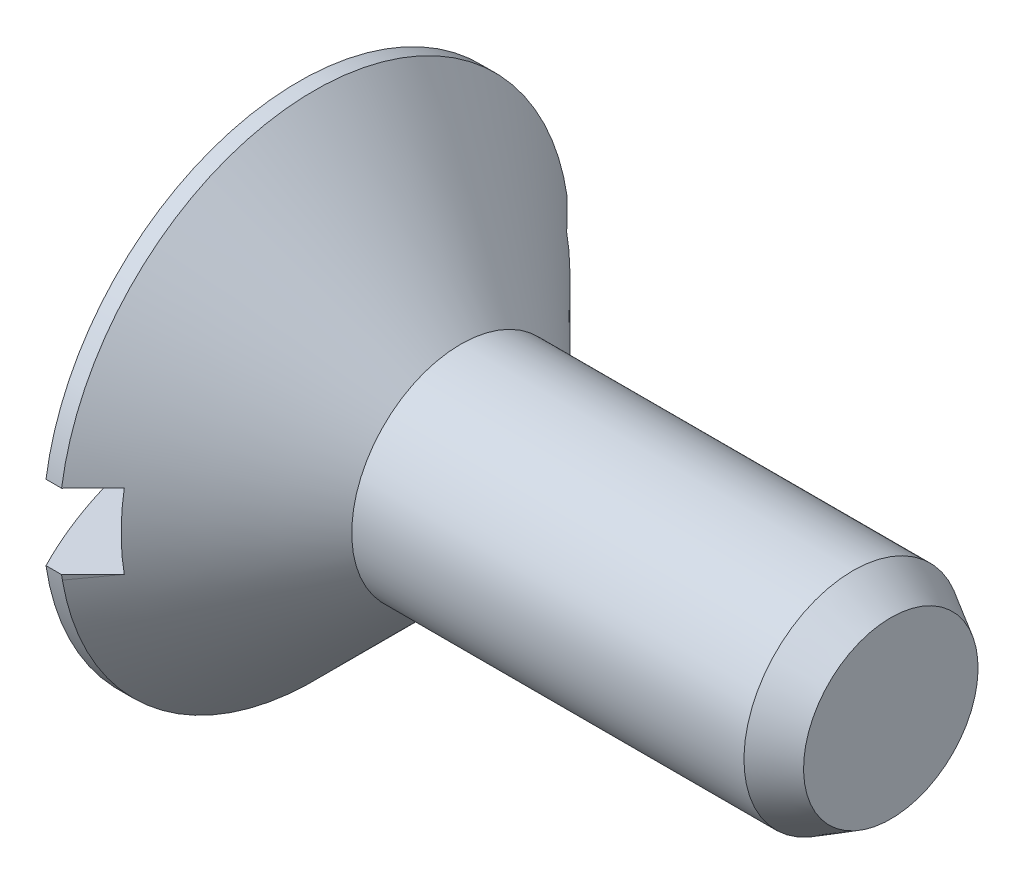
SolidWorks part; units mm, degrees
ref_plane "Front" through (0, 0, 0) normal (0, 0, 1) x (1, 0, 0)
ref_plane "Top" through (0, 0, 0) normal (0, 1, 0) x (1, 0, 0)
ref_plane "Right" through (0, 0, 0) normal (1, 0, 0) x (0, 0, -1)
sketch "Sketch1" plane through (0, 0, 0) normal (0, 0, 1) x (1, 0, 0)
  line L0 (0, 4.1) -> (0.25, 4.1)
  line L1 (0.25, 4.1) -> (2.6, 1.75)
  line L2 (2.6, 1.75) -> (9.5, 1.75)
  line L3 (9.5, 1.75) -> (9.5, 0)
  line L4 (9.5, 0) -> (0, 0)
  line L5 (0, 0) -> (0, 4.1) construction
  line L6 (6.6207, 0) -> (-1, 0) construction
  line L7 (-1, 0) -> (-1, -0.1422) construction
  line L8 (0, 0) -> (-1, 0)
  arc A1 (0, 4.1) -> (-1, 0) centre (7.905, 0) ccw
  dimension "D1" = 45
  dimension "k" = 2.6
revolve "Revolve1" add sketch "Sketch1" angle 360 about L6
cosmetic thread "ThreadCosmetic" [suppressed] parameters "D2"=3.2
sketch "Sketch2" plane through (0, 0, 0) normal (0, 0, 1) x (1, 0, 0)
  line L1 (-1, 0.6) -> (0.75, 0.6)
  line L2 (-1, 0.6) -> (-1, -0.6)
  line L3 (-1, -0.6) -> (0.75, -0.6)
  line L4 (0.75, 0.6) -> (0.75, -0.6)
  line L5 (0, 0) -> (-1, 0) construction
  arc A0 (0, 4.1) -> (-1, 0) centre (7.905, 0) ccw construction
  dimension "n" = 1.2
  dimension "t" = 1.75
extrude "Cut-Extrude1" cut sketch "Sketch2" against normal through all and the other way through all
chamfer "Chamfer1" distance 0.35 angle 60 1 edges at (9.5, 1.75, 0) first distance on face at (9.5, 1.75, 0)
sketch "Sketch4" plane through (0, 0, 0) normal (0, 0, 1) x (1, 0, 0)
  line L0 (3.0424, 1.6) -> (2.7347, 1.6)
  line L1 (2.7347, 1.6) -> (2.6481, 1.75)
  line L2 (3.0424, 1.6) -> (3.129, 1.75)
  line L3 (2.6481, 1.75) -> (2.6481, 2)
  line L4 (3.129, 1.75) -> (3.129, 2)
  line L5 (2.6481, 2) -> (3.129, 2)
  line L6 (2.8886, 1.6) -> (2.8886, 0) construction
  line L7 (0, 0) -> (7.3035, 0) construction
  line L9 (2.6, 1.75) -> (2.6, -1.75) construction
  line L12 (8.8938, 1.75) -> (2.6, 1.75) construction
  dimension "D2" = 60
  dimension "D3" = 0.25
  dimension "minordia" = 3.2
  dimension "threadstart" = 0.2886
revolve "ThreadSchematic" [suppressed] cut sketch "Sketch4" angle 360 about L7
pattern_linear "ThdSchPat" [suppressed] count 15 spacing 0.4809 along (1, 0, 0) of bodies 137
sketch "Sketch3" plane through (0, 0, 0) normal (0, 0, 1) x (1, 0, 0)
  line L0 (2.6, 1.75) -> (9.5, 1.75) construction
  line L2 (7.5, 1.75) -> (8, 1.75) construction
  line L3 (9.5, 1.75) -> (9.5, 0) construction
  line L4 (8, 1.75) -> (9.5, 0)
  line L5 (2.9, 0) -> (5.4301, 0) construction
  line L6 (9.5, 0) -> (9.7, 0)
  line L7 (9.7, 0) -> (9.7, 1.75)
  line L8 (9.7, 1.75) -> (9.5, 1.75)
  line L9 (8, 1.75) -> (9.5, 1.75)
  dimension "D1" = 0.5
revolve "EndCone" [suppressed] cut sketch "Sketch3" angle 360 about L5
equation "\"minordia@Sketch4\" = \"D2@ThreadCosmetic\""
equation "\"D1@Chamfer1\" = \"d@Sketch1\" / 10"
equation "\"D1@Sketch3\" = \"y@Sketch3\" / 4"
equation "\"threadstart@Sketch4\" = \"advance@Sketch4\"*0.6"
equation "\"D1@ThdSchPat\" = int(((\"l@Sketch1\"-\"k@Sketch1\")/\"advance@Sketch4\") + 0.999)"
equation "\"D3@ThdSchPat\" = \"advance@Sketch4\""
